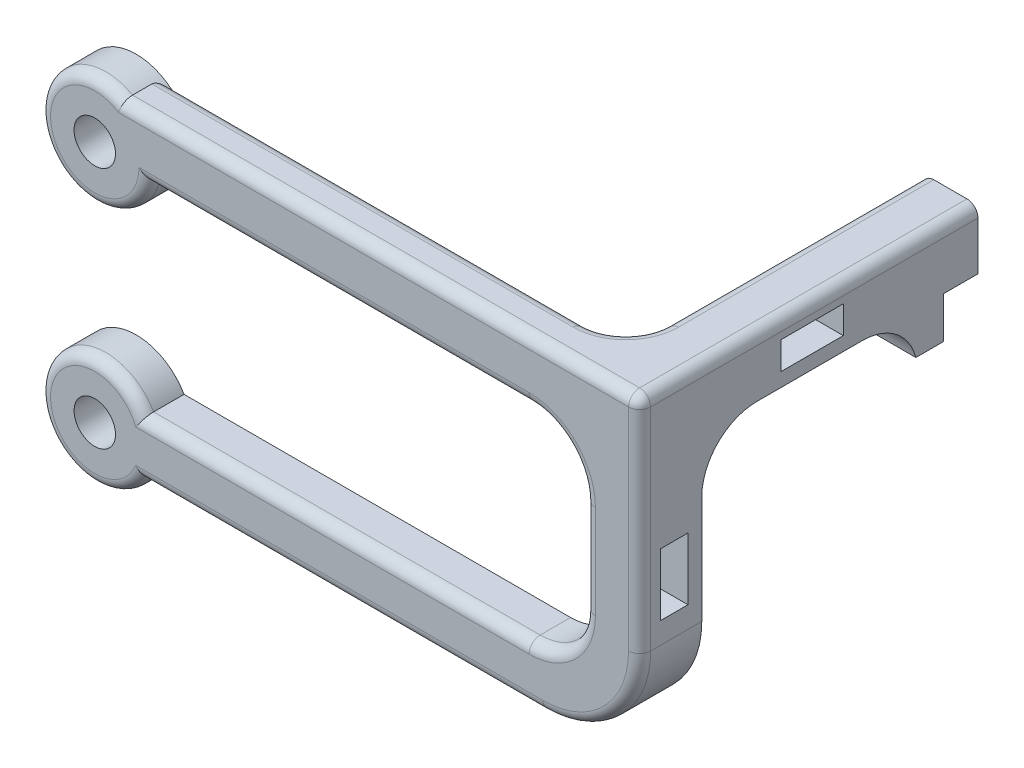
SolidWorks part; units mm, degrees
ref_plane "Front Plane" through (0, 0, 0) normal (0, 0, 1) x (1, 0, 0)
ref_plane "Top Plane" through (0, 0, 0) normal (0, 1, 0) x (1, 0, 0)
ref_plane "Right Plane" through (0, 0, 0) normal (1, 0, 0) x (0, 0, -1)
sketch "Sketch1" plane through (0, 0, 0) normal (0, 0, 1) x (1, 0, 0)
  line L0 (-4.95, 8.8) -> (32.5, 8.8) construction
  line L1 (32.5, 8.8) -> (32.5, 7) construction
  line L2 (34, 7) -> (31, 7) construction
  line L3 (32.5, 7) -> (32.5, -8.8) construction
  line L4 (32.5, -8.8) -> (-4.95, -8.8) construction
  line L5 (34.5, 6.8) -> (34.5, -6.8) construction
  line L6 (-1.4859, 6.8) -> (34.5, 6.8)
  line L7 (-1.4859, 6.8) -> (-1.4859, 10.8)
  line L8 (-1.4859, 10.8) -> (34.5, 10.8)
  line L9 (34.5, 6.8) -> (34.5, 10.8)
  line L10 (-1.4859, 6.8) -> (34.5, 10.8) construction
  line L11 (-1.4859, 10.8) -> (34.5, 6.8) construction
  line L12 (-1.4859, -10.8) -> (34.5, -10.8)
  line L13 (-1.4859, -10.8) -> (-1.4859, -6.8)
  line L14 (-1.4859, -6.8) -> (34.5, -6.8)
  line L15 (34.5, -10.8) -> (34.5, -6.8)
  line L16 (-1.4859, -10.8) -> (34.5, -6.8) construction
  line L17 (-1.4859, -6.8) -> (34.5, -10.8) construction
  line L19 (30.5, 6.8) -> (34.5, 6.8)
  line L20 (30.5, 6.8) -> (30.5, -6.8)
  line L21 (30.5, -6.8) -> (34.5, -6.8)
  line L22 (34.5, 6.8) -> (34.5, -6.8)
  circle A1 centre (-4.95, 8.8) radius 1.5
  circle A2 centre (-4.95, -8.8) radius 1.5
  circle A3 centre (-4.95, 8.8) radius 4
  circle A4 centre (-4.95, -8.8) radius 4
  point P8 (16.5071, 8.8)
  point P18 (16.5071, -8.8)
  point P27 (35.8251, 6.8)
  dimension "D1" = 3
  dimension "D2" = 8
  dimension "D3" = 4
  dimension "D4" = 2
  dimension "D5" = 4
extrude "Boss-Extrude1" add sketch "Sketch1" along normal blind 3 contours L7 A3 A1 | L13 A4 A2 | A4 L12 L15 L14 | L13 A4 | L7 A3 | A3 L6 L9 L8 | L22 L6 L20 L14 region at (16.6879, 8.8, 0) region at (-8.8406, 8.8, 0) region at (-1.2703, 8.8, 0) region at (32.5, 0, 0) region at (16.6879, -8.8, 0) region at (-1.2703, -8.8, 0) region at (-1.5953, -8.8, 0)
sketch "Sketch2" plane through (34.5, 0, 0) normal (1, 0, 0) x (0, 0, -1)
  line L0 (-3, -10.8) -> (0, -10.8) construction
  line L1 (0, 10.8) -> (1.5, 10.8)
  line L2 (0, 10.8) -> (0, -10.8)
  line L3 (0, -10.8) -> (1.5, -10.8)
  line L4 (1.5, 10.8) -> (1.5, -10.8)
  circle A0 centre (9.5, 0) radius 7 construction
  circle A1 centre (9.5, 0) radius 7 construction
  point P8 (0, -10.8)
  dimension "D1" = 1
extrude "Boss-Extrude2" add sketch "Sketch2" against normal up to surface (4 mm away) up to face at (30.5, 0, 1.5)
sketch "Sketch3" plane through (34.5, 0, 0) normal (1, 0, 0) x (0, 0, -1)
  line L1 (1.5, 10.8) -> (13.5, 10.8) construction
  line L2 (1.5, 10.8) -> (1.5, 8)
  line L3 (1.5, 8) -> (13.5, 8)
  line L4 (13.5, 10.8) -> (13.5, 8)
  line L5 (13.5, 10.8) -> (-3, 10.8)
  line L6 (13.5, 10.8) -> (13.5, 12.3)
  line L7 (13.5, 12.3) -> (-3, 12.3)
  line L8 (-3, 10.8) -> (-3, 12.3)
  circle A0 centre (9.5, 0) radius 7 construction
  point P10 (-3, 10.8)
  line M6 (1.5, -10.8) -> (1.5, 10.8)
  line M7 (1.5, 10.8) -> (-3, 10.8)
  dimension "D1" = 1
  dimension "D2" = 12
  dimension "D3" = 1.5
extrude "Boss-Extrude3" add sketch "Sketch3" against normal up to surface (4 mm away) contours L8 L5 L6 L7 M7 | L4 L5 L3 M6 region at (34.5, 9.4, -7.5) region at (34.5, 11.55, -5.25) up to face at (30.5, 0, 0.375)
sketch "Sketch4" plane through (34.5, 0, 0) normal (1, 0, 0) x (0, 0, -1)
  line L0 (-3, 0) -> (9.5, 0) construction
  line L2 (9.5, 0) -> (9.5, 12.3) construction
  line L4 (13.5, 12.3) -> (-3, 12.3) construction
  line L5 (7.25, 9) -> (11.75, 9)
  line L6 (7.25, 9) -> (7.25, 11)
  line L7 (7.25, 11) -> (11.75, 11)
  line L8 (11.75, 9) -> (11.75, 11)
  line L9 (7.25, 9) -> (11.75, 11) construction
  line L10 (7.25, 11) -> (11.75, 9) construction
  line L11 (0.5, -2.25) -> (-1.5, -2.25)
  line L12 (0.5, -2.25) -> (0.5, 2.25)
  line L13 (0.5, 2.25) -> (-1.5, 2.25)
  line L14 (-1.5, -2.25) -> (-1.5, 2.25)
  line L15 (0.5, -2.25) -> (-1.5, 2.25) construction
  line L16 (0.5, 2.25) -> (-1.5, -2.25) construction
  line L17 (1.5, 8) -> (13.5, 8) construction
  line L18 (1.5, -10.8) -> (1.5, 8) construction
  line L19 (-3, -10.8) -> (-3, 12.3) construction
  point P2 (-3, 0)
  point P5 (9.5, 10)
  point P7 (9.5, 12.3)
  point P13 (-0.5, 0)
  point P18 (0, 0)
  dimension "D1" = 4.5
  dimension "D2" = 2
  dimension "D3" = 1
  dimension "D4" = 1
extrude "Cut-Extrude1" cut sketch "Sketch4" against normal blind 3.5
sketch "Sketch5" plane through (0, 0, 3) normal (0, 0, 1) x (1, 0, 0)
  line L0 (30.5, 12.3) -> (-3.0135, 12.3)
  line L1 (30.5, 12.3) -> (30.5, 10.8) construction
  line L2 (-1.4859, 10.8) -> (30.5, 10.8) construction
  line L3 (30.5, 12.3) -> (30.5, 10.8)
  line L4 (-1.4859, 10.8) -> (30.5, 10.8)
  arc A0 (-1.4859, 10.8) -> (-1.4859, 6.8) centre (-4.95, 8.8) ccw construction
  arc A1 (-1.4859, 10.8) -> (-1.4859, 6.8) centre (-4.95, 8.8) ccw
  line M6 (30.5, 12.3) -> (30.5, 10.8)
  line M7 (30.5, 10.8) -> (-1.4859, 10.8)
  arc M8 (-1.4859, 10.8) -> (-1.4859, 6.8) centre (-4.95, 8.8) ccw
extrude "Boss-Extrude4" add sketch "Sketch5" against normal up to surface (3 mm away) contours L0 M6 M8 M7 region at (14.192, 11.5557, 3) up to face at (-3.45, 8.8, 0)
sketch "Sketch6" plane through (0, 0, 3) normal (0, 0, 1) x (1, 0, 0)
  line L0 (30.5, 8) -> (34.5, 8) construction
  line L1 (30.5, 8) -> (34.5, 8) construction
  line L2 (-1.0308, 8) -> (30.5, 8)
  line L3 (30.5, 8) -> (30.5, 6.8)
  line L4 (30.5, 6.8) -> (-1.4859, 6.8)
  arc A0 (-3.0135, 12.3) -> (-1.4859, 6.8) centre (-4.95, 8.8) ccw construction
  arc A1 (-3.0135, 12.3) -> (-1.0308, 8) centre (-4.95, 8.8) ccw
  point P7 (-0.9956, 9.4024)
  line M8 (-1.4859, 6.8) -> (30.5, 6.8)
extrude "Cut-Extrude2" cut sketch "Sketch6" against normal through all contours A1 L3 L2 M8 region at (14.639, 7.3986, 3)
fillet "Fillet1" radius 4 2 edges at (30.5, -6.8, 1.5) (30.5, 8, 1.5)
fillet "Fillet2" radius 7 1 edges at (34.5, -10.8, 0.75)
fillet "Fillet3" radius 3 1 edges at (30.5, 8.15, 0)
fillet "Fillet4" radius 3 1 edges at (30.5, -6.4623, 0)
fillet "Fillet5" radius 4 1 edges at (32.299, 8, -1.5)
fillet "Fillet6" radius 0.8 15 edges at (12.2432, 12.3, 0) (29.6213, 12.3, -0.8787) (34.5, 4.25, 3) (32.4497, -8.7497, 3) (12.5071, -6.8, 3) (29.3284, -5.6284, 3) (30.5, 0.6, 3) (29.3284, 6.8284, 3) (30.5, 12.3, -8.25) (34.5, 12.3, -5.25) (13.0071, -10.8, 3) (-8.95, -8.8, 3) (12.7346, 8, 3) (-8.5825, 7.1251, 3) (15.7432, 12.3, 3)
sketch "Sketch7" plane through (0, 0, -13.5) normal (0, 0, -1) x (-1, 0, 0)
  line L5 (-30.5, 8) -> (-30.5, 11.5)
  line L6 (-31.3, 12.3) -> (-33.7, 12.3)
  line L7 (-34.5, 11.5) -> (-34.5, 8)
  line L8 (-34.5, 8) -> (-30.5, 8)
  line L9 (-30.5, 8) -> (-30.5, 11.5)
  line L10 (-31.3, 12.3) -> (-33.7, 12.3)
  line L11 (-34.5, 11.5) -> (-34.5, 8)
  line L12 (-34.5, 8) -> (-30.5, 8)
  arc A2 (-30.5, 11.5) -> (-31.3, 12.3) centre (-31.3, 11.5) ccw
  arc A3 (-33.7, 12.3) -> (-34.5, 11.5) centre (-33.7, 11.5) ccw
  arc A4 (-30.5, 11.5) -> (-31.3, 12.3) centre (-31.3, 11.5) ccw
  arc A5 (-33.7, 12.3) -> (-34.5, 11.5) centre (-33.7, 11.5) ccw
  dimension "D1" = 0
extrude "Boss-Extrude5" add sketch "Sketch7" along normal blind 8
sketch "Sketch9" plane through (0, 8, 0) normal (0, -1, 0) x (1, 0, 0)
  line L0 (30.5, -21.5) -> (30.5, -5.5) construction
  line L1 (30.5, -19) -> (34.5, -19)
  line L2 (30.5, -19) -> (30.5, -17)
  line L3 (30.5, -17) -> (34.5, -17)
  line L4 (34.5, -19) -> (34.5, -17)
  line L6 (34.5, -5.5) -> (34.5, -21.5) construction
  line L7 (34.5, -21.5) -> (30.5, -21.5) construction
  point P6 (30.5, -18.55)
  point P10 (0, 0)
  point P11 (0, 0)
  dimension "D1" = 2.5
  dimension "D2" = 2
extrude "Boss-Extrude6" add sketch "Sketch9" along normal blind 3
fillet "Fillet7" radius 4 1 edges at (32.5, 8, -17)
